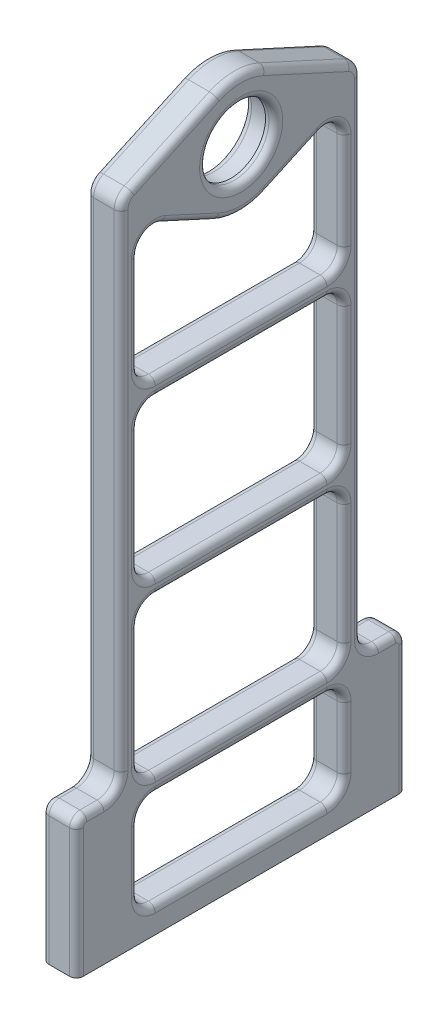
SolidWorks part; units mm, degrees
ref_plane "Front Plane" through (0, 0, 0) normal (0, 0, 1) x (1, 0, 0)
ref_plane "Top Plane" through (0, 0, 0) normal (0, 1, 0) x (1, 0, 0)
ref_plane "Right Plane" through (0, 0, 0) normal (1, 0, 0) x (0, 0, -1)
sketch "Croquis1" plane through (0, 0, 0) normal (1, 0, 0) x (0, 0, -1)
  line L0 (3.1865, 95.253) -> (51.7799, 95.253) construction
  line L1 (15, 74) -> (5, 64)
  line L2 (0, 0) -> (5, 0)
  line L3 (0, 0) -> (0, 155)
  line L4 (0, 155) -> (5, 155)
  line L5 (5, 0) -> (5, 155)
  line L6 (5, 155) -> (91, 155)
  line L7 (5, 155) -> (5, 150)
  line L8 (5, 150) -> (91, 150)
  line L9 (91, 155) -> (91, 150)
  line L10 (91, 155) -> (96, 155)
  line L11 (91, 155) -> (91, 0)
  line L12 (91, 0) -> (96, 0)
  line L13 (96, 155) -> (96, 0)
  line L14 (13, 305) -> (18, 305)
  line L15 (13, 305) -> (13, 79)
  line L16 (13, 79) -> (18, 79)
  line L17 (18, 305) -> (18, 79)
  line L18 (5, 79) -> (91, 79)
  line L19 (5, 79) -> (5, 74)
  line L20 (5, 74) -> (91, 74)
  line L21 (91, 79) -> (91, 74)
  line L22 (83, 79) -> (78, 79)
  line L23 (83, 79) -> (83, 305)
  line L24 (83, 305) -> (78, 305)
  line L25 (78, 79) -> (78, 305)
  line L26 (18, 305) -> (78, 305)
  line L27 (18, 305) -> (18, 300)
  line L28 (18, 300) -> (78, 300)
  line L29 (78, 305) -> (78, 300)
  line L30 (18, 205) -> (78, 205)
  line L31 (18, 205) -> (18, 200)
  line L32 (18, 200) -> (78, 200)
  line L33 (78, 205) -> (78, 200)
  line L34 (18, 255) -> (78, 255)
  line L35 (18, 255) -> (18, 250)
  line L36 (18, 250) -> (78, 250)
  line L37 (78, 255) -> (78, 250)
  line L38 (18, 122) -> (78, 122)
  line L39 (18, 122) -> (18, 107)
  line L40 (18, 107) -> (78, 107)
  line L41 (78, 122) -> (78, 107)
  line L42 (81, 74) -> (91, 64)
  line L43 (78, 52.6217) -> (83, 52.6217) construction
  line L45 (48, 155) -> (48, 150) construction
  line L46 (48, 200) -> (48, 205) construction
  line L47 (48, 255) -> (48, 250) construction
  line L48 (48, 250) -> (48, 255) construction
  line L49 (48, 305) -> (48, 300) construction
  line L50 (22.0711, 74) -> (5, 56.9289)
  line L51 (73.9289, 74) -> (91, 56.9289)
  line L52 (48, 300) -> (48, 255) construction
  line L53 (48, 250) -> (48, 205) construction
  line L54 (48, 205) -> (48, 334.4288) construction
  line L55 (48, 200) -> (48, 155) construction
  line L56 (48, 150) -> (48, 122) construction
  line L57 (48, 107) -> (48, 79) construction
  line L58 (48, 74) -> (48, 0) construction
  line L59 (13, 150) -> (5, 142)
  line L60 (83, 150) -> (91, 142)
  point P59 (48, 79)
  point P64 (48, 74)
  dimension "D2" = 70
  dimension "D3" = 5
  dimension "D4" = 45
  dimension "D5" = 45
  dimension "D6" = 5
  dimension "D7" = 5
  dimension "D8" = 5
  dimension "D9" = 10
  dimension "D10" = 10
  dimension "D11" = 45
  dimension "D12" = 45
  dimension "D13" = 8
  dimension "D14" = 74
  dimension "D15" = 15
  dimension "D16" = 150
extrude "Saliente-Extruir1" add sketch "Croquis1" along normal blind 10 contours L2 L5 L4 L3 | L50 L20 L1 L5 | L5 L20 L11 L18 L16 | L13 L10 L9 L11 L12 | L20 L51 L11 L42 | L25 L18 L23 L8 | L17 L8 L15 L16 | L17 L40 L25 L38 | L15 L6 L5 L8 | L17 L6 L15 L8 | L8 L25 L6 L17 | L17 L14 L15 L6 | L25 L8 L23 L6 | L25 L6 L23 L24 | L23 L8 L9 L6 | L17 L28 L25 L26 | L17 L36 L25 L34 | L17 L32 L25 L30 | L59 L8 L5 | L8 L60 L11 | L20 L5 L1 | L20 L42 L11
sketch "Croquis2" plane through (10, 0, 0) normal (1, 0, 0) x (0, 0, -1)
  line L0 (48, 301.5) -> (34.0198, 331.4807) construction
  line L1 (48, 301.5) -> (81.08, 301.5) construction
  line L2 (48, 73.5) -> (48, 301.5) construction
  line L3 (106.66, 301.5) -> (55.5, 301.5)
  line L4 (22.42, 73.5) -> (22.42, 301.5)
  line L5 (73.58, 301.5) -> (73.58, 136.78) construction
  line L6 (106.66, 301.5) -> (106.66, 272.7)
  line L7 (106.66, 272.7) -> (55.5, 272.7)
  line L8 (55.5, 301.5) -> (55.5, 272.7)
  line L9 (22.42, 301.5) -> (22.42, 73.5) construction
  line L10 (8.4398, 331.4807) -> (59.5998, 331.4807)
  line L11 (8.4398, 331.4807) -> (8.4398, 302.6807)
  line L12 (8.4398, 302.6807) -> (59.5998, 302.6807)
  line L13 (59.5998, 331.4807) -> (59.5998, 302.6807)
  line L18 (73.58, 136.78) -> (73.58, 73.5) construction
  line L19 (48, 73.5) -> (14.92, 73.5) construction
  line L20 (-10.66, 73.5) -> (40.5, 73.5)
  line L21 (-10.66, 73.5) -> (-10.66, 44.7)
  line L22 (-10.66, 44.7) -> (40.5, 44.7)
  line L23 (40.5, 73.5) -> (40.5, 44.7)
  line L24 (36.4002, 43.5193) -> (87.5602, 43.5193)
  line L25 (36.4002, 43.5193) -> (36.4002, 14.7193)
  line L26 (36.4002, 14.7193) -> (87.5602, 14.7193)
  line L27 (87.5602, 43.5193) -> (87.5602, 14.7193)
  line L28 (48, 73.5) -> (61.9802, 43.5193) construction
  line L29 (62.5413, 301.5) -> (55.5, 295.71)
  line L30 (55.5, 295.71) -> (59.5573, 272.7)
  line L32 (52.5584, 331.4807) -> (59.5998, 325.6907)
  line L33 (59.5998, 325.6907) -> (55.5425, 302.6807)
  line L34 (73.58, 73.5) -> (73.58, 301.5)
  line L35 (-10.66, 124.84) -> (40.5, 124.84)
  line L36 (-10.66, 124.84) -> (-10.66, 96.04)
  line L37 (-10.66, 96.04) -> (40.5, 96.04)
  line L38 (40.5, 124.84) -> (40.5, 96.04)
  line L39 (55.5, 96.14) -> (106.66, 96.14)
  line L40 (55.5, 96.14) -> (55.5, 67.34)
  line L41 (55.5, 67.34) -> (106.66, 67.34)
  line L42 (106.66, 96.14) -> (106.66, 67.34)
  line L43 (-10.66, 176.18) -> (40.5, 176.18)
  line L44 (-10.66, 176.18) -> (-10.66, 147.38)
  line L45 (-10.66, 147.38) -> (40.5, 147.38)
  line L46 (40.5, 176.18) -> (40.5, 147.38)
  line L47 (-10.66, 227.52) -> (40.5, 227.52)
  line L48 (-10.66, 227.52) -> (-10.66, 198.72)
  line L49 (-10.66, 198.72) -> (40.5, 198.72)
  line L50 (40.5, 227.52) -> (40.5, 198.72)
  line L51 (-10.66, 278.86) -> (40.5, 278.86)
  line L52 (-10.66, 278.86) -> (-10.66, 250.06)
  line L53 (-10.66, 250.06) -> (40.5, 250.06)
  line L54 (40.5, 278.86) -> (40.5, 250.06)
  line L55 (55.5, 250.16) -> (106.66, 250.16)
  line L56 (55.5, 250.16) -> (55.5, 221.36)
  line L57 (55.5, 221.36) -> (106.66, 221.36)
  line L58 (106.66, 250.16) -> (106.66, 221.36)
  line L59 (55.5, 198.82) -> (106.66, 198.82)
  line L60 (55.5, 198.82) -> (55.5, 170.02)
  line L61 (55.5, 170.02) -> (106.66, 170.02)
  line L62 (106.66, 198.82) -> (106.66, 170.02)
  line L63 (55.5, 147.48) -> (106.66, 147.48)
  line L64 (55.5, 147.48) -> (55.5, 118.68)
  line L65 (55.5, 118.68) -> (106.66, 118.68)
  line L66 (106.66, 147.48) -> (106.66, 118.68)
  line L67 (13, 301.5) -> (83, 301.5) construction
  line L70 (13, 305) -> (13, 155) construction
  line L71 (83, 155) -> (83, 305) construction
  line L73 (18, 300) -> (78, 300) construction
  circle A2 centre (48, 301.5) radius 25.58
  circle A3 centre (48, 73.5) radius 25.58
  arc A4 (22.42, 73.5) -> (73.58, 73.5) centre (48, 73.5) ccw
  arc A5 (73.58, 301.5) -> (22.42, 301.5) centre (48, 301.5) ccw
  point P8 (48, 187.5)
  point P9 (48, 301.5)
  point P11 (81.08, 301.5)
  point P20 (34.0198, 331.4807)
  point P34 (61.9802, 43.5193)
  point P37 (14.92, 73.5)
  point P52 (22.42, 124.84)
  point P53 (73.58, 96.14)
  point P58 (14.92, 124.84)
  point P59 (81.08, 96.14)
  point P80 (22.42, 278.86)
  point P81 (22.42, 227.52)
  point P82 (22.42, 176.18)
  point P83 (73.58, 250.16)
  point P84 (73.58, 198.82)
  point P85 (73.58, 147.48)
  point P86 (14.92, 278.86)
  point P87 (14.92, 227.52)
  point P88 (14.92, 176.18)
  point P93 (81.08, 250.16)
  point P94 (81.08, 198.82)
  point P95 (81.08, 147.48)
  dimension "D1" = 51.16
  dimension "D3" = 51.16
  dimension "D7" = 33.08
  dimension "D30" = 228
  dimension "D4" = 115
  dimension "D5" = 28.8
  dimension "D6" = 115
  dimension "D8" = 140.57
  dimension "D9" = 140.57
  dimension "D10" = 23.01
  dimension "D11" = 23.01
  dimension "D12" = 10
  dimension "D13" = 10
  dimension "D14" = 7.5
  dimension "D15" = 7.5
  dimension "D16" = 51.34
  dimension "D17" = 7.5
  dimension "D18" = 7.5
  dimension "D19" = 7.5
  dimension "D20" = 7.5
  dimension "D21" = 7.5
  dimension "D22" = 7.5
  dimension "D23" = 51.34
  dimension "D24" = 51.34
  dimension "D25" = 51.34
  dimension "D26" = 51.34
  dimension "D27" = 51.34
  dimension "D28" = 51.34
  dimension "D29" = 51.34
  dimension "D31" = 1.5
sketch "Croquis3" plane through (10, 0, 0) normal (1, 0, 0) x (0, 0, -1)
  line L0 (13, 301.5) -> (83, 301.5) construction
  line L1 (106.66, 301.5) -> (55.5, 301.5) construction
  line L2 (13, 305) -> (13, 155) construction
  line L3 (83, 155) -> (83, 305) construction
  line L5 (15.9167, 306.0453) -> (40.7083, 317.4085)
  line L6 (80.0833, 306.0453) -> (55.2917, 317.4085)
  line L7 (15.9167, 296.9547) -> (40.7083, 285.5915)
  line L8 (80.0833, 296.9547) -> (55.2917, 285.5915)
  line L9 (14.4293, 305) -> (13, 305)
  line L10 (13, 305) -> (83, 305) construction
  line L11 (13, 305) -> (13, 301.5)
  line L12 (81.5707, 305) -> (83, 305)
  line L13 (83, 305) -> (83, 301.5)
  circle A0 centre (48, 301.5) radius 10.01
  circle A1 centre (48, 301.5) radius 11.01
  circle A2 centre (48, 301.5) radius 17.5
  circle A3 centre (18, 301.5) radius 5
  circle A4 centre (78, 301.5) radius 5
  line M13 (78, 300) -> (78, 255)
  line M15 (18, 255) -> (18, 300)
  line M16 (18, 300) -> (78, 300)
  line M18 (83, 305) -> (13, 305)
  dimension "D1" = 22.02
  dimension "D2" = 20.02
  dimension "D3" = 35
  dimension "D4" = 10
extrude "Saliente-Extruir2" add sketch "Croquis3" against normal up to surface (10 mm away) contours A2 A1 M18 | A3 A2 L5 M18 | A3 M18 | A3 M18 M15 M16 | A3 M15 M16 | A3 L7 A2 M15 M16 | A2 A1 M16 | A4 A2 L8 M16 M13 | A4 L6 A2 M18 | A3 A2 M16 M18 | A2 A1 M18 M16 | A2 A1 M16 M18 | A4 A2 M18 M16 | A4 M16 M13 | A4 M18 M16 M13 | A4 M18 up to face at (0, 227.5, -48)
sketch "Croquis7" plane through (10, 0, 0) normal (1, 0, 0) x (0, 0, -1)
  line L0 (14.4293, 305) -> (13, 305)
  line L1 (22.0711, 74) -> (73.9289, 74)
  line L7 (81.5707, 305) -> (83, 305)
  line L12 (22.0711, 74) -> (73.9289, 74)
  line L29 (83, 155) -> (83, 305)
  line L30 (83, 155) -> (83, 305)
  line L31 (83, 305) -> (81.5707, 305)
  line L32 (83, 305) -> (81.5707, 305)
  line L33 (80.0833, 306.0453) -> (55.2917, 317.4085)
  line L34 (80.0833, 306.0453) -> (55.2917, 317.4085)
  line L35 (40.7083, 317.4085) -> (15.9167, 306.0453)
  line L36 (40.7083, 317.4085) -> (15.9167, 306.0453)
  line L37 (14.4293, 305) -> (13, 305)
  line L38 (14.4293, 305) -> (13, 305)
  line L39 (13, 305) -> (13, 155)
  line L40 (13, 305) -> (13, 155)
  line L41 (13, 155) -> (0, 155)
  line L42 (13, 155) -> (0, 155)
  line L43 (0, 155) -> (0, 0)
  line L44 (0, 155) -> (0, 0)
  line L45 (0, 0) -> (5, 0)
  line L46 (0, 0) -> (5, 0)
  line L47 (5, 0) -> (5, 56.9289)
  line L48 (5, 0) -> (5, 56.9289)
  line L49 (5, 56.9289) -> (22.0711, 74)
  line L50 (5, 56.9289) -> (22.0711, 74)
  line L51 (73.9289, 74) -> (91, 56.9289)
  line L52 (73.9289, 74) -> (91, 56.9289)
  line L53 (91, 56.9289) -> (91, 0)
  line L54 (91, 56.9289) -> (91, 0)
  line L55 (91, 0) -> (96, 0)
  line L56 (91, 0) -> (96, 0)
  line L57 (96, 0) -> (96, 155)
  line L58 (96, 0) -> (96, 155)
  line L59 (96, 155) -> (83, 155)
  line L60 (96, 155) -> (83, 155)
  circle A0 centre (18, 301.5) radius 5
  arc A1 (15.9167, 306.0453) -> (14.4293, 305) centre (18, 301.5) ccw
  circle A7 centre (78, 301.5) radius 5
  arc A12 (15.9167, 306.0453) -> (14.4293, 305) centre (18, 301.5) ccw
  arc A15 (81.5707, 305) -> (80.0833, 306.0453) centre (78, 301.5) ccw
  arc A16 (81.5707, 305) -> (80.0833, 306.0453) centre (78, 301.5) ccw
  arc A17 (55.2917, 317.4085) -> (40.7083, 317.4085) centre (48, 301.5) ccw
  arc A18 (55.2917, 317.4085) -> (40.7083, 317.4085) centre (48, 301.5) ccw
  dimension "D1" = 0
extrude "Cortar-Extruir5" cut sketch "Croquis7" against normal through all both and the other way through all contours A7 L30 L7 | A0 L0 L40
pattern_linear "MatrizL2" count 2 spacing 228 along (0, -1, 0) of "Saliente-Extruir2"
sketch "Croquis10" plane through (10, 0, 0) normal (1, 0, 0) x (0, 0, -1)
  line L0 (96, 0) -> (96, 155) construction
  line L1 (0, 0) -> (96, 0)
  line L2 (0, 0) -> (0, 7.2193)
  line L3 (0, 7.2193) -> (96, 7.2193)
  line L4 (96, 0) -> (96, 7.2193)
  line L5 (36.4002, 14.7193) -> (87.5602, 14.7193) construction
  dimension "D1" = 7.5
extrude "Cortar-Extruir6" cut sketch "Croquis10" against normal through all both and the other way through all
sketch "Croquis11" plane through (10, 0, 0) normal (1, 0, 0) x (0, 0, -1)
  line L0 (0, 7.2193) -> (-20, 7.2193)
  line L1 (-20, 7.2193) -> (0, 17.2193)
  line L2 (0, 155) -> (0, 0) construction
  line L3 (0, 17.2193) -> (0, 7.2193)
  line L4 (48, 73.5) -> (48, -15.6705) construction
  line L5 (96, 7.2193) -> (116, 7.2193)
  line L6 (96, 17.2193) -> (96, 7.2193)
  line L7 (116, 7.2193) -> (96, 17.2193)
  dimension "D1" = 20
  dimension "D2" = 10
extrude "Saliente-Extruir4" add sketch "Croquis11" against normal up to surface (10 mm away) contours L3 L1 L0 | L5 L7 L6 up to face at (0, 92.0682, -48)
sketch "Croquis12" plane through (0, 7.2193, 0) normal (0, -1, 0) x (1, 0, 0)
  line L1 (0, -5) -> (0, 20) construction
  circle A0 centre (5, 10) radius 2
  dimension "D1" = 4
  dimension "D2" = 10
  dimension "D3" = 5
extrude "Cortar-Extruir7" cut sketch "Croquis12" against normal through all both and the other way through all
ref_plane "Plano3" through (0, 0, -48) normal (0, 0, 1) x (1, 0, 0)
mirror "Simetría1" about plane through (0, 0, -48) normal (0, 0, 1) of "Cortar-Extruir7"
sketch "Croquis16" plane through (0, 0, 0) normal (-1, 0, 0) x (0, 0, 1)
  circle A0 centre (-48, 301.5) radius 11.01
  circle A1 centre (-48, 73.5) radius 11.01
extrude "Cortar-Extruir8" cut sketch "Croquis16" against normal through all both and the other way through all
sketch "Croquis17" plane through (10, 0, 0) normal (1, 0, 0) x (0, 0, -1)
  circle A0 centre (48, 301.5) radius 11.01
  circle A1 centre (48, 301.5) radius 10.1
  circle A2 centre (48, 73.5) radius 11.01
  circle A3 centre (48, 73.5) radius 10.1
  dimension "D1" = 20.2
  dimension "D2" = 20.2
extrude "Saliente-Extruir5" add sketch "Croquis17" against normal blind 2 contours A0 A1 | A2 A3
sketch "Croquis18" plane through (10, 0, 0) normal (1, 0, 0) x (0, 0, -1)
  line L0 (18, 295.9998) -> (40.7083, 285.5915) construction
  line L1 (18, 295.9998) -> (18, 255) construction
  line L2 (78, 295.9998) -> (55.2917, 285.5915) construction
  line L3 (78, 255) -> (78, 295.9998) construction
  line L4 (18, 107) -> (18, 79.0002) construction
  line L5 (18, 79.0002) -> (40.7083, 89.4085) construction
  line L6 (78, 79.0002) -> (55.2917, 89.4085) construction
  line L7 (78, 79.0002) -> (78, 107) construction
  line L8 (78, 67.9998) -> (55.2917, 57.5915) construction
  line L9 (73.9289, 74) -> (91, 56.9289) construction
  line L10 (5, 56.9289) -> (22.0711, 74) construction
  line L11 (18, 67.9998) -> (40.7083, 57.5915) construction
  line L12 (55.2917, 317.4085) -> (80.0833, 306.0453)
  line L13 (55.2917, 317.4085) -> (80.0833, 306.0453)
  line L14 (83, 301.5) -> (83, 155)
  line L15 (83, 301.5) -> (83, 155)
  line L16 (83, 155) -> (96, 155)
  line L17 (83, 155) -> (96, 155)
  line L18 (96, 155) -> (96, 17.2193)
  line L19 (96, 155) -> (96, 17.2193)
  line L20 (96, 17.2193) -> (116, 7.2193)
  line L21 (96, 17.2193) -> (116, 7.2193)
  line L22 (116, 7.2193) -> (91, 7.2193)
  line L23 (116, 7.2193) -> (91, 7.2193)
  line L24 (91, 7.2193) -> (91, 56.9289)
  line L25 (91, 7.2193) -> (91, 56.9289)
  line L26 (91, 56.9289) -> (79.266, 68.6629)
  line L27 (91, 56.9289) -> (79.266, 68.6629)
  line L28 (78, 68.5) -> (78, 67.9998)
  line L29 (78, 68.5) -> (78, 67.9998)
  line L30 (78, 67.9998) -> (55.2917, 57.5915)
  line L31 (78, 67.9998) -> (55.2917, 57.5915)
  line L32 (91, 7.2193) -> (116, 7.2193)
  line L33 (116, 7.2193) -> (96, 17.2193)
  line L34 (96, 17.2193) -> (96, 155)
  line L35 (96, 155) -> (83, 155)
  line L36 (83, 155) -> (83, 301.5)
  line L37 (80.0833, 306.0453) -> (55.2917, 317.4085)
  line L38 (40.7083, 317.4085) -> (15.9167, 306.0453)
  line L39 (13, 301.5) -> (13, 155)
  line L40 (13, 155) -> (0, 155)
  line L41 (0, 155) -> (0, 17.2193)
  line L42 (0, 17.2193) -> (-20, 7.2193)
  line L43 (-20, 7.2193) -> (5, 7.2193)
  line L44 (5, 7.2193) -> (5, 56.9289)
  line L45 (5, 56.9289) -> (16.734, 68.6629)
  line L46 (18, 68.5) -> (18, 67.9998)
  line L47 (18, 67.9998) -> (40.7083, 57.5915)
  line L48 (55.2917, 57.5915) -> (78, 67.9998)
  line L49 (78, 67.9998) -> (78, 68.5)
  line L50 (79.266, 68.6629) -> (91, 56.9289)
  line L51 (91, 56.9289) -> (91, 7.2193)
  line L52 (91, 7.2193) -> (116, 7.2193)
  line L53 (116, 7.2193) -> (96, 17.2193)
  line L54 (96, 17.2193) -> (96, 155)
  line L55 (96, 155) -> (83, 155)
  line L56 (83, 155) -> (83, 301.5)
  line L57 (80.0833, 306.0453) -> (55.2917, 317.4085)
  line L58 (40.7083, 317.4085) -> (15.9167, 306.0453)
  line L59 (13, 301.5) -> (13, 155)
  line L60 (13, 155) -> (0, 155)
  line L61 (0, 155) -> (0, 17.2193)
  line L62 (0, 17.2193) -> (-20, 7.2193)
  line L63 (-20, 7.2193) -> (5, 7.2193)
  line L64 (5, 7.2193) -> (5, 56.9289)
  line L65 (5, 56.9289) -> (16.734, 68.6629)
  line L66 (18, 68.5) -> (18, 67.9998)
  line L67 (18, 67.9998) -> (40.7083, 57.5915)
  line L68 (55.2917, 57.5915) -> (78, 67.9998)
  line L69 (78, 67.9998) -> (78, 68.5)
  line L70 (79.266, 68.6629) -> (91, 56.9289)
  line L71 (91, 56.9289) -> (91, 7.2193)
  line L72 (40.7083, 57.5915) -> (18, 67.9998)
  line L73 (40.7083, 57.5915) -> (18, 67.9998)
  line L74 (18, 67.9998) -> (18, 68.5)
  line L75 (18, 67.9998) -> (18, 68.5)
  line L76 (16.734, 68.6629) -> (5, 56.9289)
  line L77 (16.734, 68.6629) -> (5, 56.9289)
  line L78 (5, 56.9289) -> (5, 7.2193)
  line L79 (5, 56.9289) -> (5, 7.2193)
  line L80 (5, 7.2193) -> (-20, 7.2193)
  line L81 (5, 7.2193) -> (-20, 7.2193)
  line L82 (-20, 7.2193) -> (0, 17.2193)
  line L83 (-20, 7.2193) -> (0, 17.2193)
  line L84 (0, 17.2193) -> (0, 155)
  line L85 (0, 17.2193) -> (0, 155)
  line L86 (0, 155) -> (13, 155)
  line L87 (0, 155) -> (13, 155)
  line L88 (13, 155) -> (13, 301.5)
  line L89 (13, 155) -> (13, 301.5)
  line L90 (15.9167, 306.0453) -> (40.7083, 317.4085)
  line L91 (15.9167, 306.0453) -> (40.7083, 317.4085)
  line L96 (78, 205) -> (78, 250)
  line L97 (18, 205) -> (78, 205)
  line L98 (18, 250) -> (18, 205)
  line L99 (78, 250) -> (18, 250)
  line L100 (78, 205) -> (78, 250)
  line L101 (18, 205) -> (78, 205)
  line L102 (18, 250) -> (18, 205)
  line L103 (78, 250) -> (18, 250)
  line L104 (78, 155) -> (78, 200)
  line L105 (18, 155) -> (78, 155)
  line L106 (18, 200) -> (18, 155)
  line L107 (78, 200) -> (18, 200)
  line L108 (78, 155) -> (78, 200)
  line L109 (18, 155) -> (78, 155)
  line L110 (18, 200) -> (18, 155)
  line L111 (78, 200) -> (18, 200)
  line L112 (78, 150) -> (18, 150)
  line L113 (78, 122) -> (78, 150)
  line L114 (18, 122) -> (78, 122)
  line L115 (18, 150) -> (18, 122)
  line L116 (78, 150) -> (18, 150)
  line L117 (78, 122) -> (78, 150)
  line L118 (18, 122) -> (78, 122)
  line L119 (18, 150) -> (18, 122)
  line L120 (83, 150) -> (83, 79)
  line L121 (91, 142) -> (83, 150)
  line L122 (91, 79) -> (91, 142)
  line L123 (83, 79) -> (91, 79)
  line L124 (83, 150) -> (83, 79)
  line L125 (91, 142) -> (83, 150)
  line L126 (91, 79) -> (91, 142)
  line L127 (83, 79) -> (91, 79)
  line L128 (13, 150) -> (5, 142)
  line L129 (13, 79) -> (13, 150)
  line L130 (5, 79) -> (13, 79)
  line L131 (5, 142) -> (5, 79)
  line L132 (13, 150) -> (5, 142)
  line L133 (13, 79) -> (13, 150)
  line L134 (5, 79) -> (13, 79)
  line L135 (5, 142) -> (5, 79)
  line L137 (18, 295.9998) -> (18, 255)
  line L138 (40.7083, 285.5915) -> (18, 295.9998)
  line L139 (78, 295.9998) -> (55.2917, 285.5915)
  line L140 (78, 255) -> (78, 295.9998)
  line L141 (18, 255) -> (78, 255)
  line L142 (18, 295.9998) -> (18, 255)
  line L143 (40.7083, 285.5915) -> (18, 295.9998)
  line L144 (78, 295.9998) -> (55.2917, 285.5915)
  line L145 (78, 255) -> (78, 295.9998)
  line L146 (18, 255) -> (78, 255)
  line L147 (78, 79.0002) -> (78, 107)
  line L148 (55.2917, 89.4085) -> (78, 79.0002)
  line L149 (18, 79.0002) -> (40.7083, 89.4085)
  line L150 (18, 107) -> (18, 79.0002)
  line L151 (78, 107) -> (18, 107)
  line L152 (78, 79.0002) -> (78, 107)
  line L153 (55.2917, 89.4085) -> (78, 79.0002)
  line L154 (18, 79.0002) -> (40.7083, 89.4085)
  line L155 (18, 107) -> (18, 79.0002)
  line L156 (78, 107) -> (18, 107)
  circle A0 centre (18.8315, 56.6183) radius 10
  circle A1 centre (77.1685, 56.6183) radius 10
  circle A2 centre (73, 86.7921) radius 5
  circle A3 centre (23, 86.7921) radius 5
  circle A4 centre (23, 288.2079) radius 5
  circle A5 centre (73, 288.2079) radius 5
  arc A6 (83, 301.5) -> (80.0833, 306.0453) centre (78, 301.5) ccw
  arc A7 (83, 301.5) -> (80.0833, 306.0453) centre (78, 301.5) ccw
  arc A8 (78, 68.5) -> (79.266, 68.6629) centre (78, 73.5) ccw
  arc A9 (78, 68.5) -> (79.266, 68.6629) centre (78, 73.5) ccw
  arc A10 (40.7083, 57.5915) -> (55.2917, 57.5915) centre (48, 73.5) ccw
  arc A11 (40.7083, 57.5915) -> (55.2917, 57.5915) centre (48, 73.5) ccw
  arc A12 (83, 301.5) -> (80.0833, 306.0453) centre (78, 301.5) ccw
  arc A13 (55.2917, 317.4085) -> (40.7083, 317.4085) centre (48, 301.5) ccw
  arc A14 (15.9167, 306.0453) -> (13, 301.5) centre (18, 301.5) ccw
  arc A15 (16.734, 68.6629) -> (18, 68.5) centre (18, 73.5) ccw
  arc A16 (40.7083, 57.5915) -> (55.2917, 57.5915) centre (48, 73.5) ccw
  arc A17 (78, 68.5) -> (79.266, 68.6629) centre (78, 73.5) ccw
  arc A18 (83, 301.5) -> (80.0833, 306.0453) centre (78, 301.5) ccw
  arc A19 (55.2917, 317.4085) -> (40.7083, 317.4085) centre (48, 301.5) ccw
  arc A20 (15.9167, 306.0453) -> (13, 301.5) centre (18, 301.5) ccw
  arc A21 (16.734, 68.6629) -> (18, 68.5) centre (18, 73.5) ccw
  arc A22 (40.7083, 57.5915) -> (55.2917, 57.5915) centre (48, 73.5) ccw
  arc A23 (78, 68.5) -> (79.266, 68.6629) centre (78, 73.5) ccw
  arc A24 (16.734, 68.6629) -> (18, 68.5) centre (18, 73.5) ccw
  arc A25 (16.734, 68.6629) -> (18, 68.5) centre (18, 73.5) ccw
  arc A26 (15.9167, 306.0453) -> (13, 301.5) centre (18, 301.5) ccw
  arc A27 (15.9167, 306.0453) -> (13, 301.5) centre (18, 301.5) ccw
  arc A28 (55.2917, 317.4085) -> (40.7083, 317.4085) centre (48, 301.5) ccw
  arc A29 (55.2917, 317.4085) -> (40.7083, 317.4085) centre (48, 301.5) ccw
  arc A31 (40.7083, 285.5915) -> (55.2917, 285.5915) centre (48, 301.5) ccw
  arc A32 (40.7083, 285.5915) -> (55.2917, 285.5915) centre (48, 301.5) ccw
  arc A33 (55.2917, 89.4085) -> (40.7083, 89.4085) centre (48, 73.5) ccw
  arc A34 (55.2917, 89.4085) -> (40.7083, 89.4085) centre (48, 73.5) ccw
  circle A35 centre (48, 301.5) radius 10.1
  circle A36 centre (48, 301.5) radius 10.1
  circle A37 centre (48, 73.5) radius 10.1
  circle A38 centre (48, 73.5) radius 10.1
  dimension "D1" = 20
  dimension "D2" = 10
  dimension "D3" = 10
  dimension "D4" = 0
  dimension "D5" = 0
  dimension "D6" = 0
  dimension "D7" = 0
  dimension "D8" = 0
  dimension "D9" = 0
  dimension "D10" = 0
  dimension "D11" = 0
  dimension "D12" = 0
  dimension "D13" = 0
extrude "Saliente-Extruir6" add sketch "Croquis18" against normal up to surface (10 mm away) contours A3 L155 L154 | A21 L77 A0 L67 L66 | A9 L29 L31 A1 L70 | A2 L153 L152 | A5 L145 L144 | A4 L143 L142 up to face at (0, 92.0682, -48)
fillet "Redondeo1" radius 5 16 edges at (5, 107, -18) (5, 107, -78) (5, 150, -18) (5, 122, -18) (5, 122, -78) (5, 150, -78) (5, 200, -78) (5, 200, -18) (5, 155, -18) (5, 155, -78) (5, 255, -18) (5, 255, -78) (5, 250, -78) (5, 250, -18) (5, 205, -18) (5, 205, -78)
fillet "Redondeo2" radius 5 2 edges at (5, 17.2193, -96) (5, 17.2193, 0)
fillet "Redondeo3" radius 2 4 edges at (5, 79, -5) (5, 79, -13) (5, 79, -83) (5, 79, -91)
fillet "Redondeo4" radius 3 2 edges at (5, 142, -5) (5, 142, -91)
fillet "Redondeo5" radius 2 2 edges at (5, 150, -83) (5, 150, -13)
fillet "Redondeo6" radius 5 2 edges at (5, 155, -83) (5, 155, -13)
fillet "Redondeo7" radius 3 2 edges at (5, 155, -96) (5, 155, 0)
fillet "Redondeo8" radius 2 92 edges at (0, 110.8787, -5) (0, 79.5858, -83.5858) (0, 79.5858, -90.4142) (0, 79.5858, -12.4142) (0, 79.5858, -5.5858) (0, 110.8787, -91) (0, 141.9054, -90.7716) (0, 141.9054, -5.2284) (0, 144.7322, -88.2678) (0, 113.0858, -13) (0, 144.7322, -7.7322) (0, 147.0193, -84.2346) (0, 147.0193, -11.7654) (0, 230.75, -83) (0, 155, -90.5) (0, 156.4645, -84.4645) (0, 156.4645, -11.5355) (0, 155, -5.5) (0, 86.1548, -96) (0, 154.1213, -0.8787) (0, 154.1213, -95.1213) (0, 304.2003, -13.7919) (0, 319, -48) (0, 311.7269, -67.6875) (0, 304.2003, -82.2081) (0, 301.5, -59.01) (0, 311.7269, -28.3125) (0, 289.1723, -63.1042) (0, 284, -48) (0, 289.1723, -32.8958) (0, 230.75, -13) (0, 73.5, -59.01) (0, 56, -48) (0, 61.6502, -31.8533) (0, 85.8277, -32.8958) (0, 61.6502, -64.1467) (0, 91, -48) (0, 85.8277, -63.1042) (0, 32.0741, -5) (0, 7.2193, 7.5) (0, 7.2193, -103.5) (0, 82.584, -20.2997) (0, 60.3092, -8.3802) (0, 66.4606, -17.0628) (0, 60.3092, -87.6198) (0, 66.4606, -78.9372) (0, 94.3961, -78) (0, 82.584, -75.7003) (0, 292.416, -75.7003) (0, 274.1039, -18) (0, 292.416, -20.2997) (0, 227.5, -78) (0, 250, -48) (0, 177.5, -78) (0, 200, -48) (0, 136, -78) (0, 150, -48) (0, 107, -48) (0, 94.3961, -18) (0, 136, -18) (0, 177.5, -18) (0, 227.5, -18) (0, 122, -48) (0, 155, -48) (0, 205, -48) (0, 255, -48) (0, 274.1039, -78) (0, 248.5355, -76.5355) (0, 32.0741, -91) (0, 198.5355, -76.5355) (0, 148.5355, -76.5355) (0, 105.5355, -76.5355) (0, 105.5355, -19.4645) (0, 148.5355, -19.4645) (0, 198.5355, -19.4645) (0, 248.5355, -19.4645) (0, 123.4645, -19.4645) (0, 123.4645, -76.5355) (0, 156.4645, -76.5355) (0, 156.4645, -19.4645) (0, 206.4645, -19.4645) (0, 256.4645, -76.5355) (0, 206.4645, -76.5355) (0, 256.4645, -19.4645) (0, 11.5284, -107.382) (0, 86.1548, 0) (0, 11.5284, 11.382) (0, 17.6809, -96.7467) (0, 17.6809, 0.7467) (0, 113.0858, -83) (0, 79, -87) (0, 79, -9)
fillet "Redondeo9" radius 2 92 edges at (10, 110.8787, -5) (10, 79.5858, -83.5858) (10, 79.5858, -90.4142) (10, 79.5858, -12.4142) (10, 79.5858, -5.5858) (10, 110.8787, -91) (10, 141.9054, -90.7716) (10, 141.9054, -5.2284) (10, 144.7322, -88.2678) (10, 113.0858, -13) (10, 144.7322, -7.7322) (10, 147.0193, -84.2346) (10, 147.0193, -11.7654) (10, 230.75, -83) (10, 155, -90.5) (10, 32.0741, -91) (10, 156.4645, -84.4645) (10, 156.4645, -11.5355) (10, 86.1548, -96) (10, 155, -5.5) (10, 154.1213, -0.8787) (10, 154.1213, -95.1213) (10, 304.2003, -13.7919) (10, 304.2003, -82.2081) (10, 311.7269, -67.6875) (10, 319, -48) (10, 311.7269, -28.3125) (10, 284, -48) (10, 230.75, -13) (10, 56, -48) (10, 91, -48) (10, 32.0741, -5) (10, 7.2193, 7.5) (10, 7.2193, -103.5) (10, 11.5284, 11.382) (10, 11.5284, -107.382) (10, 301.5, -58.1) (10, 73.5, -58.1) (10, 85.8277, -32.8958) (10, 82.584, -20.2997) (10, 61.6502, -31.8533) (10, 60.3092, -8.3802) (10, 66.4606, -17.0628) (10, 61.6502, -64.1467) (10, 60.3092, -87.6198) (10, 66.4606, -78.9372) (10, 85.8277, -63.1042) (10, 94.3961, -78) (10, 82.584, -75.7003) (10, 289.1723, -63.1042) (10, 292.416, -75.7003) (10, 289.1723, -32.8958) (10, 274.1039, -18) (10, 292.416, -20.2997) (10, 227.5, -78) (10, 250, -48) (10, 177.5, -78) (10, 200, -48) (10, 136, -78) (10, 150, -48) (10, 107, -48) (10, 94.3961, -18) (10, 136, -18) (10, 177.5, -18) (10, 227.5, -18) (10, 122, -48) (10, 155, -48) (10, 205, -48) (10, 255, -48) (10, 274.1039, -78) (10, 248.5355, -76.5355) (10, 198.5355, -76.5355) (10, 148.5355, -76.5355) (10, 105.5355, -76.5355) (10, 105.5355, -19.4645) (10, 148.5355, -19.4645) (10, 198.5355, -19.4645) (10, 248.5355, -19.4645) (10, 123.4645, -19.4645) (10, 123.4645, -76.5355) (10, 156.4645, -76.5355) (10, 156.4645, -19.4645) (10, 206.4645, -19.4645) (10, 256.4645, -76.5355) (10, 206.4645, -76.5355) (10, 256.4645, -19.4645) (10, 86.1548, 0) (10, 17.6809, -96.7467) (10, 17.6809, 0.7467) (10, 113.0858, -83) (10, 79, -87) (10, 79, -9)
sketch "Croquis20" plane through (8, 0, 0) normal (-1, 0, 0) x (0, 0, 1)
  circle A1 centre (-48, 73.5) radius 11.01
  circle A2 centre (-48, 73.5) radius 11.01
  circle A3 centre (-48, 301.5) radius 11.01
  circle A4 centre (-48, 301.5) radius 11.01
  circle A5 centre (-48, 301.5) radius 10.1
  circle A6 centre (-48, 301.5) radius 10.1
  circle A7 centre (-48, 73.5) radius 10.1
  circle A8 centre (-48, 73.5) radius 10.1
  dimension "D1" = 0
  dimension "D2" = 0
  dimension "D3" = 0
  dimension "D4" = 0
extrude "Saliente-Extruir7" add sketch "Croquis20" along normal blind 1
sketch "Croquis21" plane through (10, 0, 0) normal (1, 0, 0) x (0, 0, -1)
  line L1 (15.4105, 76.046) -> (2.4564, 76.046)
  line L2 (15.4105, 76.046) -> (15.4105, 149.9027)
  line L3 (15.4105, 149.9027) -> (2.4564, 149.9027)
  line L4 (2.4564, 76.046) -> (2.4564, 149.9027)
  line L5 (80.5365, 149.9027) -> (93.4188, 149.9027)
  line L6 (80.5365, 149.9027) -> (80.5365, 76.4841)
  line L7 (80.5365, 76.4841) -> (93.4188, 76.4841)
  line L8 (93.4188, 149.9027) -> (93.4188, 76.4841)
extrude "Saliente-Extruir8" add sketch "Croquis21" against normal up to surface (10 mm away) up to face at (0, 301.5, -61.01)
sketch "Croquis23" plane through (10, 0, 0) normal (1, 0, 0) x (0, 0, -1)
  line L0 (46.0313, 120) -> (46.0313, 109) construction
  line L1 (-45.0555, 114.5) -> (138.9876, 114.5)
  line L2 (-45.0555, 114.5) -> (-45.0555, -9.5741)
  line L3 (-45.0555, -9.5741) -> (138.9876, -9.5741)
  line L4 (138.9876, 114.5) -> (138.9876, -9.5741)
  line L5 (73, 120) -> (23, 120) construction
  line L6 (23, 109) -> (73, 109) construction
  point P10 (46.0313, 114.5)
extrude "Cortar-Extruir9" cut sketch "Croquis23" against normal through all
sketch "Croquis24" plane through (0, 114.5, 0) normal (0, -1, 0) x (1, 0, 0)
  line L0 (0, -94) -> (0, -2) construction
  line L1 (7.5, -93) -> (2.5, -93)
  line L2 (7.5, -93) -> (7.5, -3)
  line L3 (7.5, -3) -> (2.5, -3)
  line L4 (2.5, -93) -> (2.5, -3)
  line L5 (10, -94) -> (10, -2) construction
  line L7 (8, 0) -> (2, 0) construction
  line L8 (2, -96) -> (8, -96) construction
  dimension "D1" = 2.5
  dimension "D2" = 2.5
  dimension "D3" = 3
  dimension "D4" = 3
extrude "Cortar-Extruir10" cut sketch "Croquis24" against normal offset from surface (5.5 mm away) 2 up to face at (5, 122, -48)
sketch "Croquis25" plane through (0, 120, 0) normal (0, -1, 0) x (1, 0, 0)
  line L0 (7.5, -93) -> (7.5, -3) construction
  line L1 (2.5, -3) -> (7.5, -3)
  line L2 (2.5, -3) -> (2.5, -13)
  line L3 (2.5, -13) -> (7.5, -13)
  line L4 (7.5, -3) -> (7.5, -13)
  line M5 (7.5, -93) -> (7.5, -3)
  line M6 (7.5, -3) -> (2.5, -3)
  line M7 (2.5, -3) -> (2.5, -93)
  dimension "D1" = 3
extrude "Cortar-Extruir11" cut sketch "Croquis25" against normal offset from surface (30 mm away) 5 contours L3 M7 M5 M6 up to face at (5, 155, -48)
mirror "Simetría2" about plane through (0, 0, -48) normal (0, 0, 1) of "Cortar-Extruir11"
sketch "Croquis27" plane through (0, 120, 0) normal (0, -1, 0) x (1, 0, 0)
  line L0 (7.5, -83) -> (7.5, -96)
  line L1 (2, -96) -> (8, -96) construction
sketch "Croquis28" plane through (7.5, 0, 0) normal (-1, 0, 0) x (0, 0, 1)
  line L0 (-88, 150) -> (-88, 114.5)
  line L1 (-83, 150) -> (-93, 150) construction
  line L2 (-93, 114.5) -> (-3, 114.5) construction
